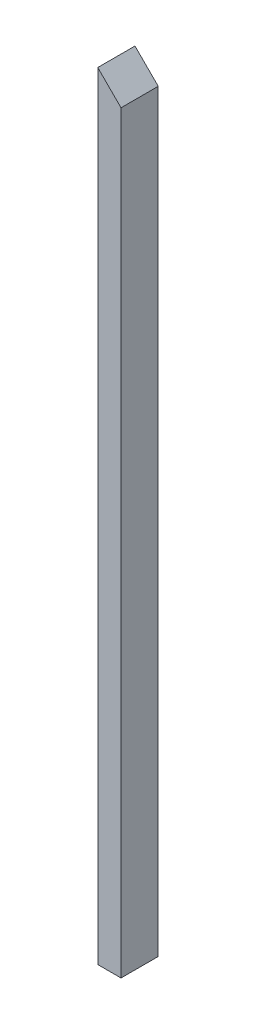
SolidWorks part; units mm, degrees
material "1023 Carbon Steel Sheet (SS)"
ref_plane "Front Plane" through (0, 0, 0) normal (0, 0, 1) x (1, 0, 0)
ref_plane "Top Plane" through (0, 0, 0) normal (0, 1, 0) x (1, 0, 0)
ref_plane "Right Plane" through (0, 0, 0) normal (1, 0, 0) x (0, 0, -1)
sketch "Sketch1" plane through (0, 0, 0) normal (0, 0, 1) x (1, 0, 0)
  line L0 (0, 0) -> (0, 2120.9)
  line L5 (0, 2120.9) -> (63.5, 2057.4)
  line L6 (63.5, 2057.4) -> (63.5, 0)
  line L7 (63.5, 0) -> (0, 0)
  dimension "D1" = 2057.4
  dimension "D2" = 45
  dimension "D3" = 63.5
extrude "Boss-Extrude1" add sketch "Sketch1" along normal blind 101.6
